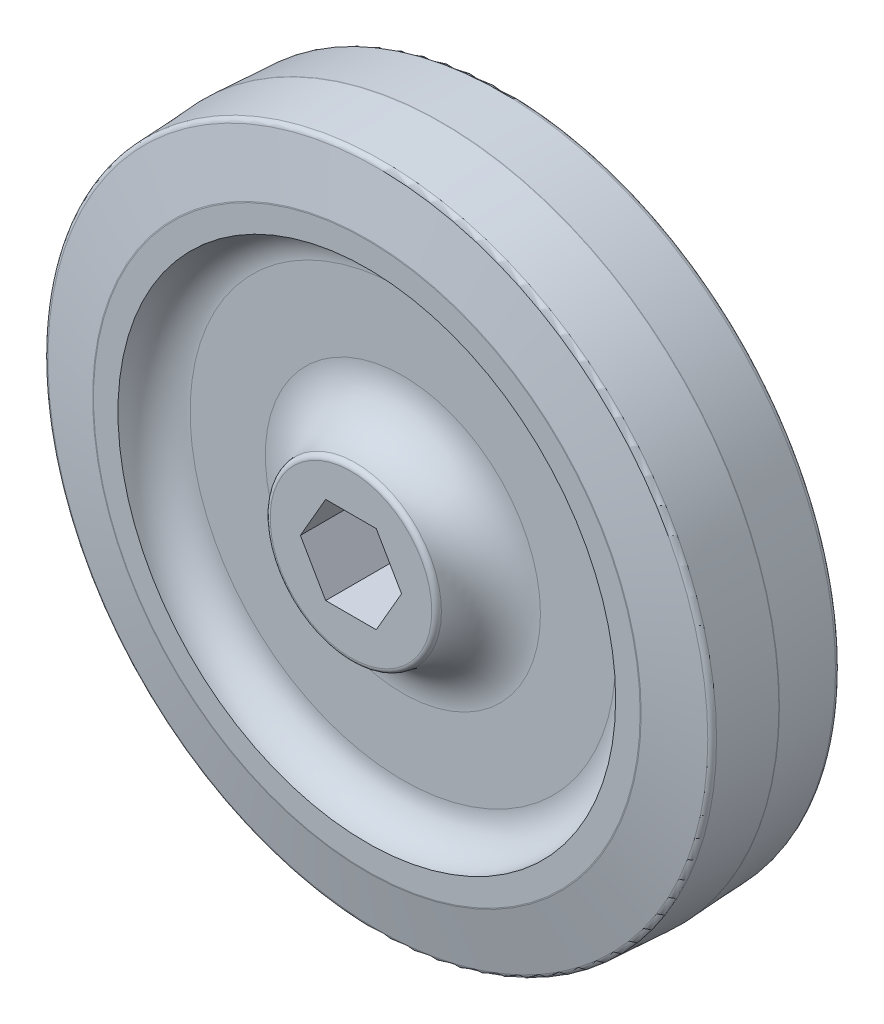
SolidWorks part; units mm, degrees
ref_plane "Front Plane" through (0, 0, 0) normal (0, 0, 1) x (1, 0, 0)
ref_plane "Top Plane" through (0, 0, 0) normal (0, 1, 0) x (1, 0, 0)
ref_plane "Right Plane" through (0, 0, 0) normal (1, 0, 0) x (0, 0, -1)
sketch "Sketch1" plane through (0, 0, 0) normal (0, 1, 0) x (1, 0, 0)
  line L0 (0, -284.5274) -> (0, 13941.8406) construction
  line L1 (0, 0) -> (12.7, 0)
  line L2 (40.6, 2.35) -> (49.5, 4.1)
  line L3 (49.5, 4.1) -> (50, 13.5)
  line L4 (50, 13.5) -> (0, 13.5) construction
  line L5 (0, 0) -> (0, 27)
  line L6 (12.7, 0) -> (12.7, 7.7)
  line L7 (12.7, 7.7) -> (36.9, 7.7)
  line L8 (36.9, 7.7) -> (36.9, 2.35)
  line L9 (36.9, 2.35) -> (40.6, 2.35)
  line L10 (49.5, 22.9) -> (50, 13.5)
  line L11 (40.6, 24.65) -> (49.5, 22.9)
  line L12 (36.9, 24.65) -> (40.6, 24.65)
  line L13 (36.9, 19.3) -> (36.9, 24.65)
  line L14 (12.7, 19.3) -> (36.9, 19.3)
  line L15 (12.7, 27) -> (12.7, 19.3)
  line L16 (0, 27) -> (12.7, 27)
  dimension "D1" = 50
  dimension "D2" = 40.6
  dimension "D3" = 22.3
  dimension "D4" = 27
  dimension "D5" = 18.8
  dimension "D6" = 8.9
  dimension "D7" = 3.7
  dimension "D8" = 12.7
  dimension "D9" = 7.7
  dimension "D10" = 5.35
revolve "Revolve1" add sketch "Sketch1" angle 360 about L0
fillet "Fillet1" radius 7.7 2 edges at (12.7, 0, -19.3) (12.7, 0, -7.7)
fillet "Fillet2" radius 5.35 2 edges at (36.9, 0, -19.3) (36.9, 0, -7.7)
fillet "Fillet3" radius 0.75 7 edges at (40.6, 0, -24.65) (49.5, 0, -4.1) (50, 0, -13.5) (49.5, 0, -22.9) (12.7, 0, -27) (40.6, 0, -2.35) (12.7, 0, 0)
sketch "Sketch2" plane through (0, 0, 0) normal (0, 0, 1) x (1, 0, 0)
  line L1 (-3.75, 6.4952) -> (-7.5, 0)
  line L2 (-7.5, 0) -> (-3.75, -6.4952)
  line L3 (-3.75, -6.4952) -> (3.75, -6.4952)
  line L4 (3.75, -6.4952) -> (7.5, 0)
  line L5 (7.5, 0) -> (3.75, 6.4952)
  line L6 (3.75, 6.4952) -> (-3.75, 6.4952)
  circle A0 centre (0, 0) radius 6.4952 construction
  point P1 (-7.2, 0)
  point P10 (-6.2354, 3.5391)
  point P11 (-3.6956, 6.2354)
  point P12 (0, 0)
  dimension "D1" = 15
extrude "Cut-Extrude1" cut sketch "Sketch2" against normal through all
